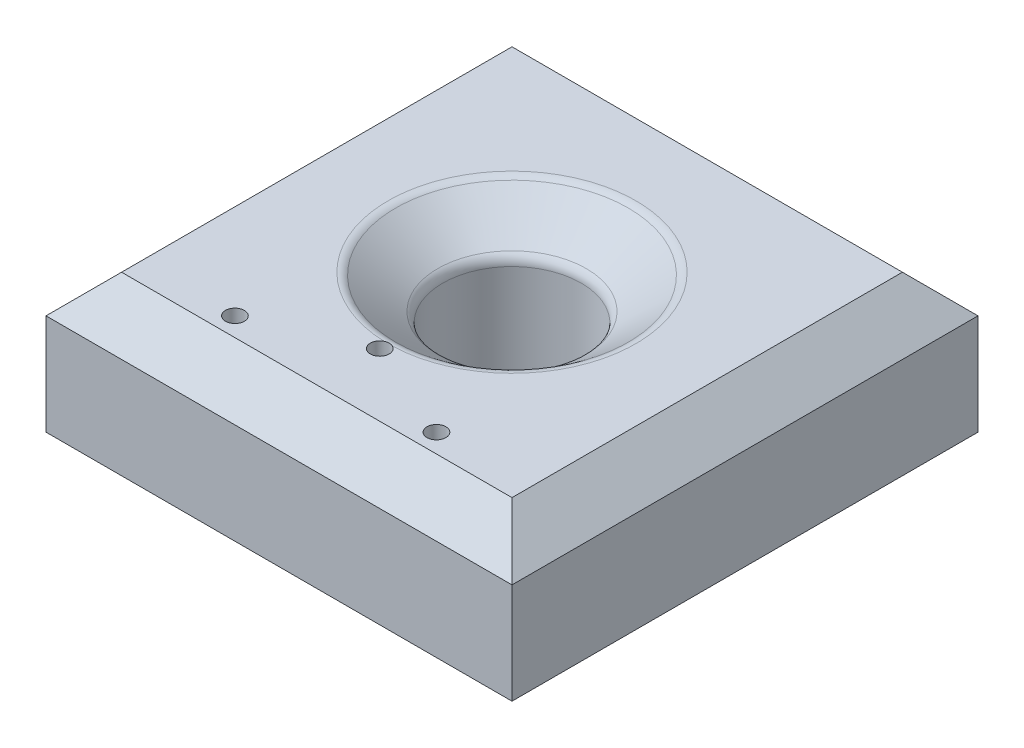
SolidWorks part; units mm, degrees
ref_plane "前视基准面" through (0, 0, 0) normal (0, 0, 1) x (1, 0, 0)
ref_plane "上视基准面" through (0, 0, 0) normal (0, 1, 0) x (1, 0, 0)
ref_plane "右视基准面" through (0, 0, 0) normal (1, 0, 0) x (0, 0, -1)
sketch "草图1" plane through (0, 0, 0) normal (0, 1, 0) x (1, 0, 0)
  line L1 (-18.5, 18.5) -> (18.5, 18.5)
  line L2 (-18.5, 18.5) -> (-18.5, -18.5)
  line L3 (-18.5, -18.5) -> (18.5, -18.5)
  line L4 (18.5, 18.5) -> (18.5, -18.5)
  line L5 (-18.5, 18.5) -> (18.5, -18.5) construction
  line L6 (-18.5, -18.5) -> (18.5, 18.5) construction
  point P0 (0, 0)
  dimension "D1" = 37
  dimension "D2" = 37
extrude "凸台-拉伸1" add sketch "草图1" along normal blind 11
sketch "草图2" plane through (0, 0, 0) normal (0, -1, 0) x (1, 0, 0)
  line L0 (-18.5, 18.5) -> (18.5, 18.5) construction
  line L1 (-18.5, -18.5) -> (-18.5, 18.5) construction
  line L2 (18.5, -18.5) -> (-18.5, -18.5) construction
  line L3 (18.5, 18.5) -> (18.5, -18.5) construction
  circle A0 centre (-16, 16) radius 1.5
  circle A1 centre (-16, -16) radius 1.5
  circle A2 centre (16, 16) radius 1.5
  circle A3 centre (16, -16) radius 1.5
  circle A4 centre (16, 4) radius 1.5
  circle A5 centre (-16, 4) radius 1.5
  circle A6 centre (0, 16) radius 1.5
  dimension "D1" = 2.5
  dimension "D2" = 2.5
  dimension "D3" = 3
  dimension "D4" = 3
  dimension "D5" = 2.5
  dimension "D6" = 2.5
  dimension "D7" = 2.5
  dimension "D8" = 3
  dimension "D9" = 2.5
  dimension "D10" = 3
  dimension "D11" = 2.5
  dimension "D12" = 3
  dimension "D13" = 2.5
  dimension "D14" = 2.5
  dimension "D15" = 12
  dimension "D16" = 3
  dimension "D17" = 2.5
  dimension "D18" = 12
  dimension "D19" = 3
  dimension "D20" = 2.5
  dimension "D21" = 0
extrude "切除-拉伸1" cut sketch "草图2" against normal blind 4
sketch "草图3" plane through (0, 0, 0) normal (0, -1, 0) x (1, 0, 0)
  circle A0 centre (0, 0) radius 5.5
  dimension "D1" = 11
extrude "切除-拉伸2" cut sketch "草图3" against normal through all
sketch "草图4" plane through (0, 0, 0) normal (0, -1, 0) x (1, 0, 0)
  line L0 (-16.5, 0.5359) -> (-16.5, -12.5359)
  line L1 (16.5, 7.4641) -> (16.5, 12.5359)
  line L2 (-3.4641, 16.5) -> (-12.5359, 16.5)
  line L8 (16.5, -16.5) -> (16.5, 16.5)
  line L9 (16.5, 16.5) -> (-16.5, 16.5)
  line L10 (-16.5, 16.5) -> (-16.5, -16.5)
  line L11 (-16.5, -16.5) -> (16.5, -16.5)
  line L12 (16.5, -12.5359) -> (16.5, 0.5359)
  line L13 (12.5359, 16.5) -> (3.4641, 16.5)
  line L14 (-16.5, 12.5359) -> (-16.5, 7.4641)
  line L15 (-12.5359, -16.5) -> (12.5359, -16.5)
  circle A2 centre (-16, 16) radius 3.5
  arc A3 (-16.5, 12.5359) -> (-12.5359, 16.5) centre (-16, 16) ccw
  circle A5 centre (-16, 4) radius 3.5
  arc A6 (-16.5, 0.5359) -> (-16.5, 7.4641) centre (-16, 4) ccw
  circle A8 centre (-16, -16) radius 3.5
  arc A9 (-12.5359, -16.5) -> (-16.5, -12.5359) centre (-16, -16) ccw
  circle A11 centre (0, 0) radius 7.5
  circle A12 centre (0, 0) radius 7.5
  circle A14 centre (0, 16) radius 3.5
  arc A15 (-3.4641, 16.5) -> (3.4641, 16.5) centre (0, 16) ccw
  circle A17 centre (16, 16) radius 3.5
  arc A18 (12.5359, 16.5) -> (16.5, 12.5359) centre (16, 16) ccw
  circle A20 centre (16, 4) radius 3.5
  arc A21 (16.5, 7.4641) -> (16.5, 0.5359) centre (16, 4) ccw
  circle A23 centre (16, -16) radius 3.5
  arc A24 (16.5, -12.5359) -> (12.5359, -16.5) centre (16, -16) ccw
  dimension "D1" = 2
  dimension "D2" = 2
  dimension "D3" = 2
  dimension "D4" = 2
  dimension "D5" = 2
  dimension "D6" = 2
  dimension "D7" = 2
  dimension "D8" = 2
  dimension "D9" = 2
extrude "切除-拉伸4" cut sketch "草图4" against normal blind 8
sketch "草图5" plane through (0, 8, 0) normal (0, -1, 0) x (1, 0, 0)
  circle A0 centre (-8, 14) radius 0.75
  circle A1 centre (0, 10.5) radius 0.75
  circle A2 centre (8, 14) radius 0.75
  dimension "D1" = 1.5
  dimension "D2" = 1.5
  dimension "D3" = 1.5
  dimension "D4" = 0
  dimension "D5" = 14
  dimension "D6" = 14
  dimension "D7" = 8
  dimension "D8" = 8
  dimension "D9" = 10.5
extrude "切除-拉伸5" cut sketch "草图5" against normal through all
sketch "草图6" plane through (0, 8, 0) normal (0, -1, 0) x (1, 0, 0)
  line L0 (-11, 12.75) -> (-3.5, 12.75)
  line L5 (-12, 11.75) -> (-4.5, 11.75)
  line L6 (-11, 17.6124) -> (-11, 12.75)
  line L7 (11, 17.6124) -> (11, 12.75)
  line L8 (12, 17.6124) -> (12, 11.75)
  line L9 (-12, 17.6124) -> (-12, 11.75)
  line L10 (-12, 17.6124) -> (-11, 17.6124)
  line L13 (12, 25.849) -> (12, 0.4173) construction
  line L15 (11, 25.849) -> (11, 0.4173) construction
  line L16 (4.5, 5.2862) -> (3.5, 5.2862)
  line L18 (-21.2509, 11.75) -> (20.9865, 11.75) construction
  line L19 (-21.2509, 12.75) -> (20.9865, 12.75) construction
  line L20 (-11, 28.0798) -> (-11, 1.8549) construction
  line L22 (-12, 28.0798) -> (-12, 1.8549) construction
  line L24 (11, 17.6124) -> (12, 17.6124)
  line L25 (-3.5, 5.2862) -> (-4.5, 5.2862)
  line L26 (4.5, 11.75) -> (4.5, 5.2862)
  line L27 (3.5, 11.75) -> (3.5, 5.2862)
  line L28 (3.5, 12.75) -> (11, 12.75)
  line L29 (4.5, 11.75) -> (12, 11.75)
  line L30 (-3.5, 11.75) -> (-3.5, 5.2862)
  line L31 (-4.5, 11.75) -> (-4.5, 5.2862)
  line L32 (-3.5, 12.75) -> (3.5, 12.75)
  line L33 (-3.5, 11.75) -> (3.5, 11.75)
  circle A6 centre (8, 14) radius 0.75 construction
  circle A7 centre (-8, 14) radius 0.75 construction
  dimension "D2" = 1.25
  dimension "D6" = 1
  dimension "D7" = 3
  dimension "D9" = 1
  dimension "D10" = 1
sketch "草图7" plane through (0, 8, 0) normal (0, -1, 0) x (1, 0, 0)
  line L0 (-4.8266, 5) -> (-4.8266, 3)
  line L1 (-13.6998, 5) -> (-4.8266, 5)
  line L2 (-13.6998, 5) -> (-13.6998, 3)
  line L3 (-13.6998, 3) -> (-4.8266, 3)
  line L4 (13.9095, 5) -> (13.9095, 3)
  line L5 (-1, -6.3066) -> (1, -6.3066)
  line L6 (-1, -6.3066) -> (-1, -17.4796)
  line L7 (-1, -17.4796) -> (1, -17.4796)
  line L8 (1, -6.3066) -> (1, -17.4796)
  line L9 (5.0122, 5) -> (5.0122, 3)
  line L10 (5.0122, 5) -> (13.9095, 5)
  line L11 (5.0122, 3) -> (13.9095, 3)
  circle A0 centre (-16, 4) radius 1.5 construction
  dimension "D1" = 2
  dimension "D2" = 2
  dimension "D3" = 1
  dimension "D4" = 1
extrude "凸台-拉伸3" add sketch "草图7" along normal blind 5
extrude "凸台-拉伸6" add sketch "草图6" along normal up to surface (8 mm away) up to face at (0, 0, 3.2143)
sketch "草图9" plane through (0, 0, 18.5) normal (0, 0, 1) x (1, 0, 0)
  line L0 (-12.5, 11) -> (-18.5, 5)
  line L1 (-18.5, 11) -> (-12.5, 11)
  line L2 (-18.5, 11) -> (-18.5, 5)
  line L5 (18.5, 11) -> (12.5, 11)
  line L6 (18.5, 11) -> (18.5, 5)
  line L9 (12.5, 11) -> (18.5, 5)
extrude "凸台-拉伸7" add sketch "草图9" against normal up to surface (37 mm away) up to face at (0, 5.5, -18.5)
sketch "草图10" plane through (-18.5, 0, 0) normal (-1, 0, 0) x (0, 0, 1)
  line L0 (-12.5, 11) -> (-18.5, 5)
  line L1 (-18.5, 11) -> (-12.5, 11)
  line L2 (-18.5, 11) -> (-18.5, 5)
  line L5 (18.5, 11) -> (12.5, 11)
  line L6 (18.5, 11) -> (18.5, 5)
  line L9 (12.5, 11) -> (18.5, 5)
extrude "凸台-拉伸8" add sketch "草图10" against normal up to surface (37 mm away) up to face at (18.5, 5.5, 0)
chamfer "倒角2" distance 3 angle 45 4 edges at (-18.5, 11, 0) (0, 11, -18.5) (18.5, 11, 0) (0, 11, 18.5)
sketch "草图11" plane through (0, 8, 0) normal (0, -1, 0) x (1, 0, 0)
  circle A2 centre (8, 14) radius 0.75
  circle A3 centre (8, 14) radius 0.75
  circle A5 centre (-8, 14) radius 0.75
  circle A6 centre (-8, 14) radius 0.75
  dimension "D1" = 0
  dimension "D2" = 0
extrude "切除-拉伸6" cut sketch "草图11" against normal through all
chamfer "倒角3" distance 3 distance2 4 1 edges at (0, 11, -5.5) first distance on face at (0, 11, -5.5)
fillet "圆角1" radius 1 1 edges at (0, 11, 9.5)
fillet "圆角2" radius 1 1 edges at (0, 8, 5.5)
equation "\"4p\"=11"
